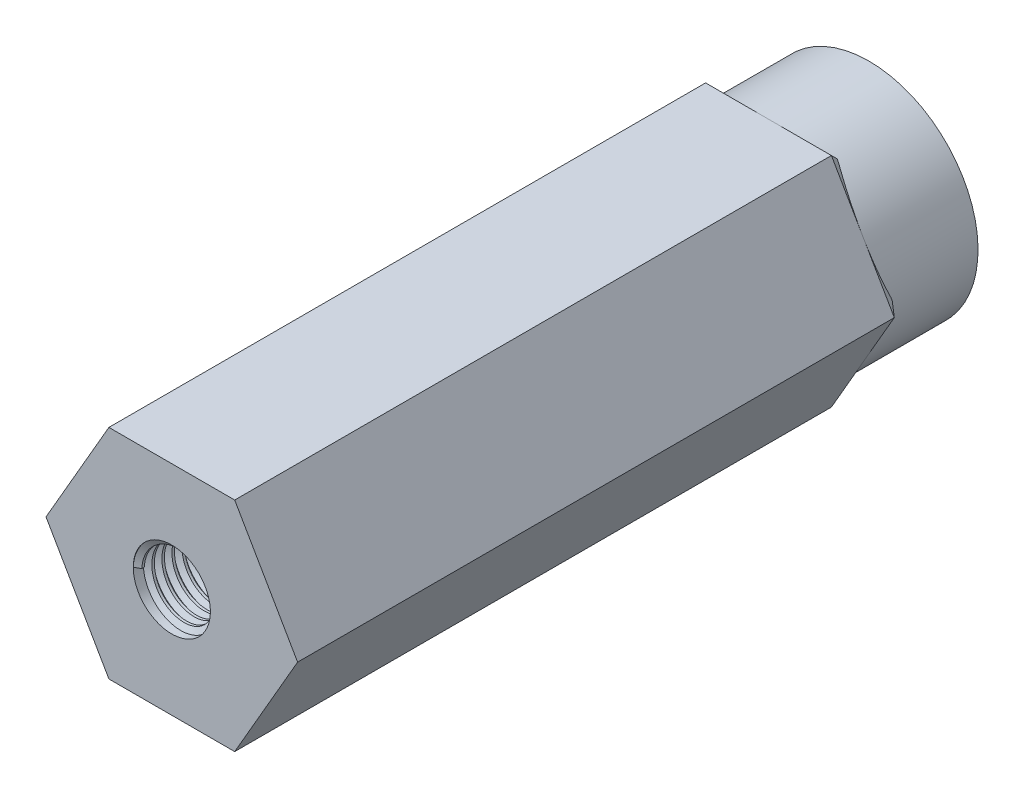
SolidWorks part; units mm, degrees
ref_plane "Alzado" through (0, 0, 0) normal (0, 0, 1) x (1, 0, 0)
ref_plane "Planta" through (0, 0, 0) normal (0, 1, 0) x (1, 0, 0)
ref_plane "Vista lateral" through (0, 0, 0) normal (1, 0, 0) x (0, 0, -1)
sketch "Croquis1" plane through (0, 0, 0) normal (0, 0, 1) x (1, 0, 0)
  line L1 (3.7528, 0) -> (1.8764, 3.25)
  line L2 (1.8764, 3.25) -> (-1.8764, 3.25)
  line L3 (-1.8764, 3.25) -> (-3.7528, 0)
  line L4 (-3.7528, 0) -> (-1.8764, -3.25)
  line L5 (-1.8764, -3.25) -> (1.8764, -3.25)
  line L6 (1.8764, -3.25) -> (3.7528, 0)
  circle A0 centre (0, 0) radius 3.25 construction
  dimension "D1" = 6.5
extrude "Saliente-Extruir1" add sketch "Croquis1" along normal blind 18.2
sketch "Croquis2" plane through (0, 0, 0) normal (0, 0, -1) x (-1, 0, 0)
  circle A0 centre (0, 0) radius 3.25
  dimension "D1" = 6.5
extrude "Saliente-Extruir2" add sketch "Croquis2" along normal blind 2.6
chamfer "Chaflán1" distance 0.4 12 edges at (-3.2837, -0.8125, 0) (-3.2837, 0.8125, 0) (-2.3455, 2.4375, 0) (-0.9382, 3.25, 0) (0.9382, 3.25, 0) (2.3455, 2.4375, 0) (3.2837, 0.8125, 0) (3.2837, -0.8125, 0) (2.3455, -2.4375, 0) (0.9382, -3.25, 0) (-0.9382, -3.25, 0) (-2.3455, -2.4375, 0)
sketch "Croquis3" plane through (0, 0, -2.6) normal (0, 0, -1) x (-1, 0, 0)
  circle A0 centre (0, 0) radius 1.75
  dimension "D1" = 3.5
extrude "Cortar-Extruir1" cut sketch "Croquis3" against normal blind 10.4
sketch "Croquis4" plane through (0, 0, 18.2) normal (0, 0, 1) x (1, 0, 0)
  circle A0 centre (0, 0) radius 1.15
  dimension "D1" = 2.3
extrude "Cortar-Extruir2" cut sketch "Croquis4" against normal blind 9.5
thread "Rosca1" pitch 0.3 method extrude profile "Perfil de rosca1" start angle 0, offset 0, length 0, pitch 0.3, diameter 2.3
ref_plane "Plano1" through (-1.15, 0, 18.2) normal (0, -1, 0) x (-1, 0, 0)
sketch "Perfil de rosca1" plane through (-1.15, 0, 18.2) normal (0, -1, 0) x (-1, 0, 0)
  line L0 (0, 0) -> (0, 0.3) construction
  line L11 (0, 0) -> (0, 0.2625)
  line L12 (0, 0.2625) -> (-0.1624, 0.1687)
  line L13 (-0.1624, 0.1687) -> (-0.1624, 0.0937)
  line L15 (-0.1624, 0.0937) -> (0, 0)
  line L17 (-0.1624, 0.1312) -> (0, 0.1312) construction
  point P2 (0, 0)
  dimension "Pitch" = 0.3
  dimension "Profile_Angle" = 60
  dimension "Profile_Land" = 0.075
  dimension "Profile_Height" = 0.1624
